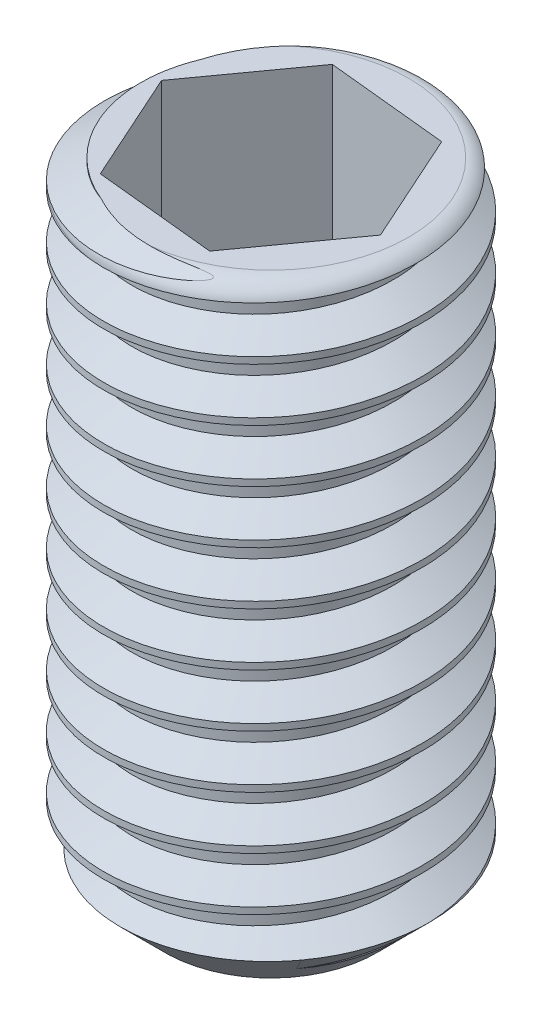
SolidWorks part; units mm, degrees
material "AISI Тип 316L нержавеющая сталь"
ref_plane "Спереди" through (0, 0, 0) normal (0, 0, 1) x (1, 0, 0)
ref_plane "Сверху" through (0, 0, 0) normal (0, 1, 0) x (1, 0, 0)
ref_plane "Справа" through (0, 0, 0) normal (1, 0, 0) x (0, 0, -1)
sketch "Эскиз1" plane through (0, 0, 0) normal (1, 0, 0) x (0, 0, -1)
  line L0 (0, 0) -> (0, 6)
  line L1 (0, 6) -> (-1.5, 6)
  line L2 (-1.5, 6) -> (-1.5, 0.5)
  line L3 (-1.5, 0.5) -> (-1, 0)
  line L4 (-1, 0) -> (0, 0)
revolve "Повернуть1" add sketch "Эскиз1" angle 360 about L0
sketch "Эскиз2" plane through (0, 6, 0) normal (0, 1, 0) x (1, 0, 0)
  line L1 (0.6747, 0.9371) -> (-0.4742, 1.0528)
  line L2 (-0.4742, 1.0528) -> (-1.1489, 0.1157)
  line L3 (-1.1489, 0.1157) -> (-0.6747, -0.9371)
  line L4 (-0.6747, -0.9371) -> (0.4742, -1.0528)
  line L5 (0.4742, -1.0528) -> (1.1489, -0.1157)
  line L6 (1.1489, -0.1157) -> (0.6747, 0.9371)
  circle A0 centre (0, 0) radius 1 construction
  dimension "D1" = 2
extrude "Вырез-Вытянуть1" cut sketch "Эскиз2" against normal blind 5
fillet "Скругление1" radius 0.2 1 edges at (0, 6, -1.5)
thread "Резьба1" pitch 0.5 method cut profile "Профиль резьбы1" start angle 0, offset 1, length 10, pitch 0.5, diameter 3
ref_plane "Плоскость1" through (1.5, -0.5, 0) normal (0, 0, 1) x (1, 0, 0)
sketch "Профиль резьбы1" plane through (1.5, -0.5, 0) normal (0, 0, 1) x (1, 0, 0)
  line L0 (0, 0) -> (0, 0.5) construction
  line L11 (0, 0) -> (0, 0.4375)
  line L12 (0, 0.4375) -> (-0.2706, 0.2812)
  line L13 (-0.2706, 0.2812) -> (-0.2706, 0.1562)
  line L15 (-0.2706, 0.1562) -> (0, 0)
  line L17 (-0.2706, 0.2187) -> (0, 0.2187) construction
  point P2 (0, 0)
  dimension "Pitch" = 0.5
  dimension "Profile_Angle" = 60
  dimension "Profile_Land" = 0.125
  dimension "Profile_Height" = 0.2706
